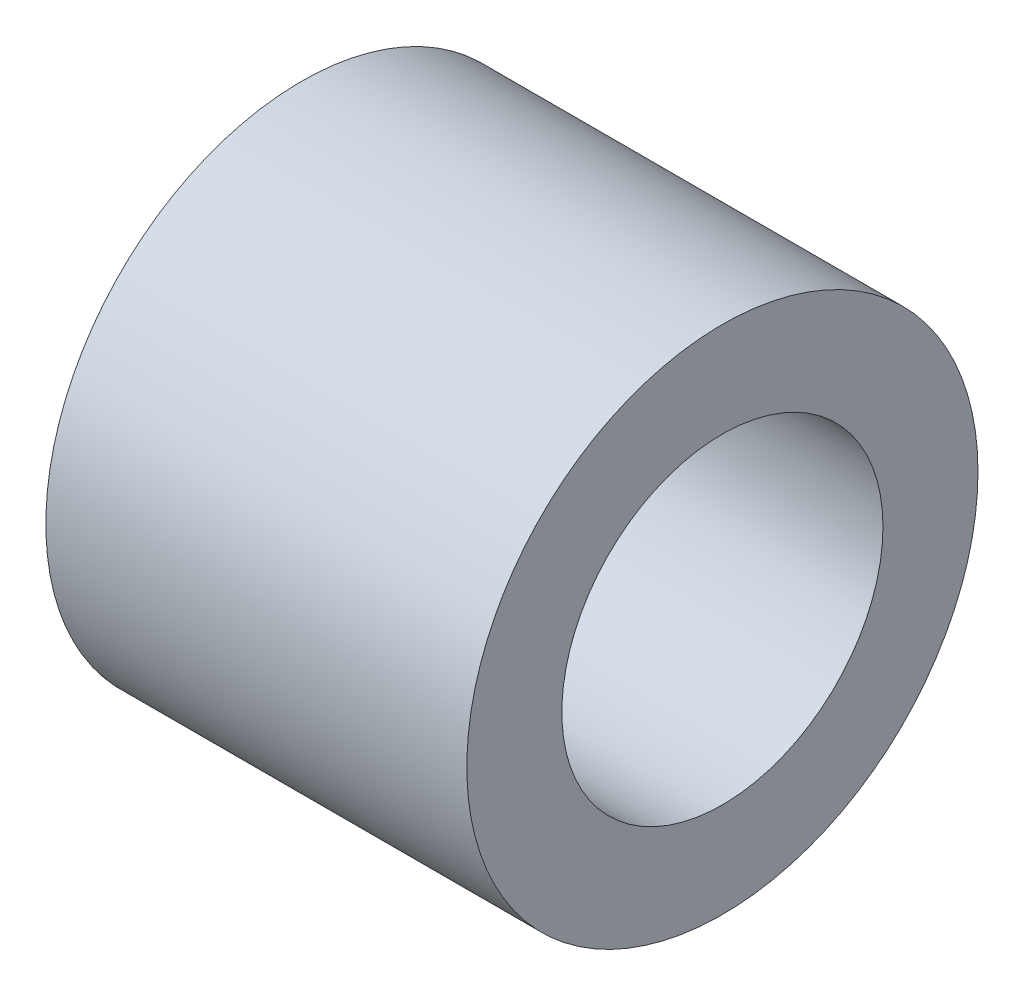
SolidWorks part; units mm, degrees
material "PLA"
ref_plane "Front Plane" through (0, 0, 0) normal (0, 0, 1) x (1, 0, 0)
ref_plane "Top Plane" through (0, 0, 0) normal (0, 1, 0) x (1, 0, 0)
ref_plane "Right Plane" through (0, 0, 0) normal (1, 0, 0) x (0, 0, -1)
sketch "Sketch1" plane through (0, 0, 0) normal (1, 0, 0) x (0, 0, -1)
  circle A0 centre (0, 0) radius 3.3909
  circle A1 centre (0, 0) radius 5.3975
  dimension "D1" = 6.7818
  dimension "D2" = 10.795
extrude "Boss-Extrude1" add sketch "Sketch1" along normal blind 8.89
